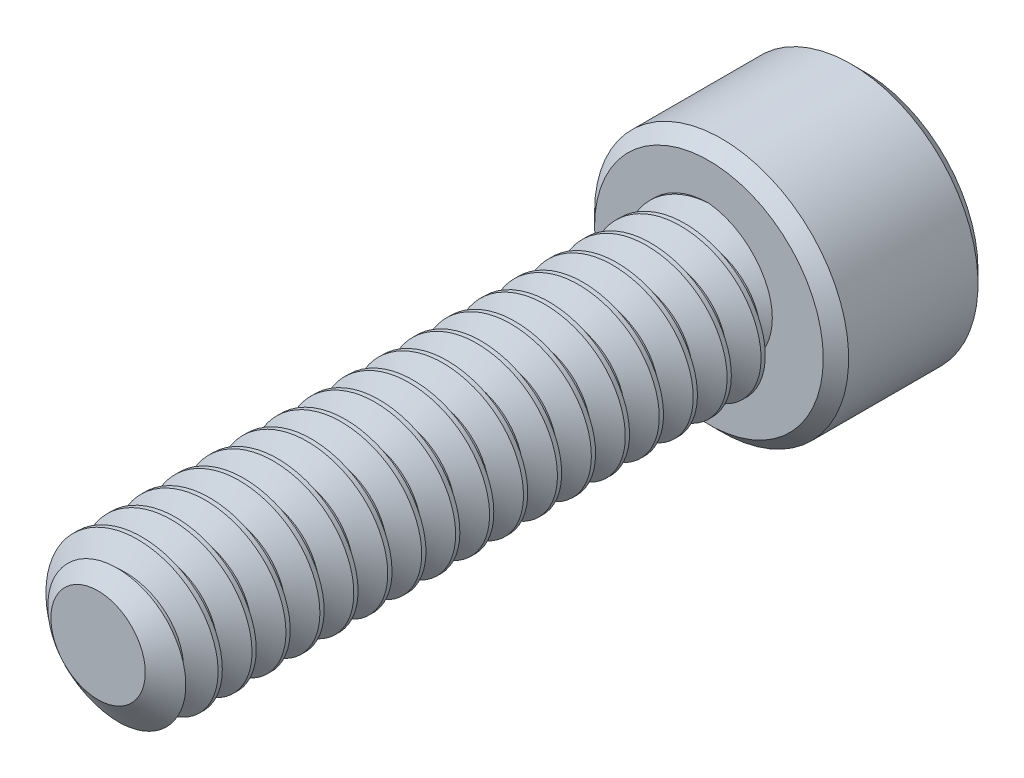
SolidWorks part; units mm, degrees
ref_plane "Front Plane" through (0, 0, 0) normal (0, 0, 1) x (1, 0, 0)
ref_plane "Top Plane" through (0, 0, 0) normal (0, 1, 0) x (1, 0, 0)
ref_plane "Right Plane" through (0, 0, 0) normal (1, 0, 0) x (0, 0, -1)
sketch "Sketch1" plane through (0, 0, 0) normal (0, 0, 1) x (1, 0, 0)
  circle A0 centre (0, 0) radius 2.413
  dimension "OD" = 4.826
extrude "Extrude1" add sketch "Sketch1" against normal blind 19.05
sketch "Sketch2" plane through (0, 0, 0) normal (0, 0, 1) x (1, 0, 0)
  circle A0 centre (0, 0) radius 2.413 construction
  circle A1 centre (0, 0) radius 2.413
curve "Helix/Spiral1" pitch 1.0583 height 20.1083 turns 19 parameters "pitch"=1.0583
sketch "Sketch3" plane through (0, 0, 0) normal (1, 0, 0) x (0, 0, -1)
  line L0 (-0.926, 2.413) -> (-0.5292, 1.7256)
  line L1 (-0.5292, 1.7256) -> (-0.3969, 1.7256)
  line L2 (-0.3969, 1.7256) -> (0, 2.413)
  line L3 (-0.926, 2.413) -> (0, 2.413)
  line L4 (-0.463, 2.413) -> (-0.463, 1.7256) construction
  line L5 (-0.7276, 2.0693) -> (-0.1984, 2.0693) construction
  line L6 (0, 2.413) -> (0, -2.413) construction
  dimension "D1" = 0.1323
  dimension "D2" = 0.5292
  dimension "D3" = 60
sweep "Cut-Sweep1" cut profiles "Sketch3" path "Helix/Spiral1"
sketch "Sketch4" plane through (0, 0, 0) normal (1, 0, 0) x (0, 0, -1)
  line L0 (0.6592, 2.413) -> (0, 1.4716)
  line L1 (0, 1.4716) -> (0, 2.413)
  line L2 (0.6592, 2.413) -> (0, 2.413)
  line L3 (-0.926, 2.413) -> (0, 2.413) construction
  line L4 (0, 0) -> (7.0209, 0) construction
  dimension "D1" = 55
  dimension "D2" = 0.254
revolve "Cut-Revolve1" cut sketch "Sketch4" angle 360 about L4
sketch "Sketch5" plane through (0, 0, 0) normal (1, 0, 0) x (0, 0, -1)
  line L0 (19.05, -1.7471) -> (19.05, 1.7217) construction
  line L1 (19.05, 2.54) -> (87.4665, 2.54)
  line L2 (19.05, 2.54) -> (19.05, 0)
  line L3 (19.05, 0) -> (87.3125, 0)
  line L4 (87.3125, 2.2098) -> (87.3125, 0)
  line L5 (87.4665, 2.54) -> (87.3125, 2.2098)
  line L6 (0, 0) -> (9.9695, 0) construction
  point P3 (87.3125, 2.54)
  point P10 (87.3125, 2.54)
  dimension "D1" = 0.3302
  dimension "Thread min" = 87.3125
  dimension "D2" = 0.127
  dimension "D3" = 25
revolve "partially thread" [suppressed] add sketch "Sketch5" angle 360 about L6
sketch "Sketch6" plane through (0, 0, -19.05) normal (0, 0, -1) x (-1, 0, 0)
  circle A0 centre (0, 0) radius 3.9624
  dimension "head dia" = 7.9248
extrude "Extrude2" add sketch "Sketch6" along normal blind 4.826
sketch "Sketch7" plane through (0, 0, -23.876) normal (0, 0, -1) x (-1, 0, 0)
  line L1 (0, 2.2914) -> (-1.9844, 1.1457)
  line L2 (-1.9844, 1.1457) -> (-1.9844, -1.1457)
  line L3 (-1.9844, -1.1457) -> (0, -2.2914)
  line L4 (0, -2.2914) -> (1.9844, -1.1457)
  line L5 (1.9844, -1.1457) -> (1.9844, 1.1457)
  line L6 (1.9844, 1.1457) -> (0, 2.2914)
  circle A0 centre (0, 0) radius 1.9844 construction
  dimension "hex dia" = 3.9688
extrude "Cut-Extrude1" cut sketch "Sketch7" against normal blind 2.9766
sketch "Sketch8" plane through (0, 0, -23.876) normal (0, 0, -1) x (-1, 0, 0)
  circle A0 centre (0, 0) radius 2.2914
extrude "Cut-Extrude2" cut sketch "Sketch8" against normal through all draft 45
chamfer "Chamfer1" distance 0.3962 angle 45 2 edges at (-3.9624, 0, -23.876) (-3.9624, 0, -19.05)
sketch "Sketch9" plane through (0, 0, 0) normal (1, 0, 0) x (0, 0, -1)
  line L0 (0, 2.413) -> (0, -2.413) construction
  line L1 (5.8208, 2.413) -> (5.8208, -2.413) construction
  dimension "D1" = 5.8208
  dimension "D4" = 0.635
  dimension "D5" = 0.3302
equation "\"D3@Helix/Spiral1\" = \"screw length@Extrude1\"+\"pitch@Helix/Spiral1\""
equation "\"D1@Sketch3\" = \"pitch@Helix/Spiral1\"*.125"
equation "\"D2@Sketch3\" = \"pitch@Helix/Spiral1\"*.5"
equation "\"D1@Cut-Extrude1\" = \"hex dia@Sketch7\"*.75"
equation "\"D1@Chamfer1\" = \"head dia@Sketch6\"*.05"
equation "\"D1@Sketch9\" = \"pitch@Helix/Spiral1\"*5.5"
